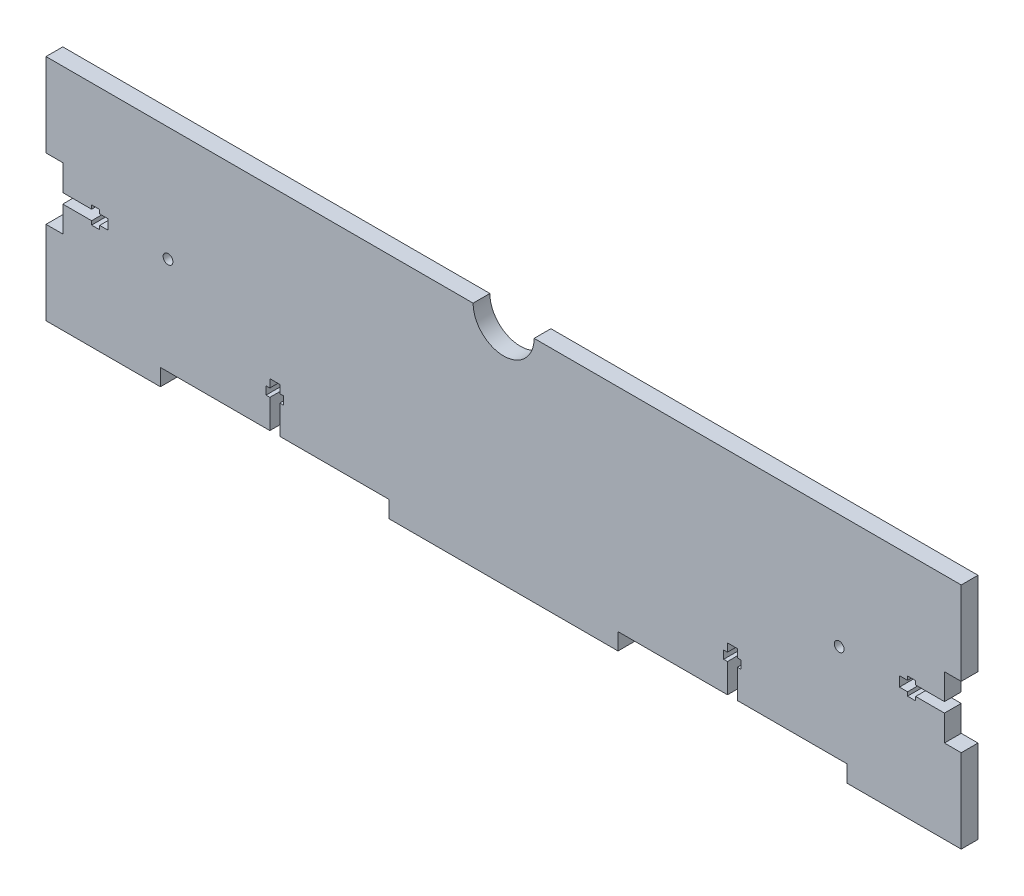
SolidWorks part; units mm, degrees
ref_plane "Front Plane" through (0, 0, 0) normal (0, 0, 1) x (1, 0, 0)
ref_plane "Top Plane" through (0, 0, 0) normal (0, 1, 0) x (1, 0, 0)
ref_plane "Right Plane" through (0, 0, 0) normal (1, 0, 0) x (0, 0, -1)
sketch "Sketch1" plane through (0, 0, 0) normal (0, 0, 1) x (1, 0, 0)
  line L0 (0, 78) -> (0, 50.625)
  line L1 (0, 50.625) -> (5.5, 50.625)
  line L2 (5.5, 50.625) -> (5.5, 42.125)
  line L3 (5.5, 42.125) -> (14.95, 42.125)
  line L4 (14.95, 42.125) -> (14.95, 43.375)
  line L5 (14.95, 43.375) -> (17.6, 43.375)
  line L6 (17.6, 43.375) -> (17.6, 42.125)
  line L7 (17.6, 42.125) -> (20.25, 42.125)
  line L8 (20.25, 42.125) -> (20.25, 38.875)
  line L9 (20.25, 38.875) -> (17.6, 38.875)
  line L10 (17.6, 38.875) -> (17.6, 37.625)
  line L11 (17.6, 37.625) -> (14.95, 37.625)
  line L12 (14.95, 37.625) -> (14.95, 38.875)
  line L13 (14.95, 38.875) -> (5.5, 38.875)
  line L14 (5.5, 38.875) -> (5.5, 30.375)
  line L15 (5.5, 30.375) -> (0, 30.375)
  line L16 (0, 30.375) -> (0, 3)
  line L17 (0, 3) -> (37.5, 3)
  line L18 (37.5, 3) -> (37.5, 8.5)
  line L19 (37.5, 8.5) -> (73.375, 8.5)
  line L20 (73.375, 8.5) -> (73.375, 17.95)
  line L21 (73.375, 17.95) -> (72.125, 17.95)
  line L22 (72.125, 17.95) -> (72.125, 20.6)
  line L23 (72.125, 20.6) -> (73.375, 20.6)
  line L24 (73.375, 20.6) -> (73.375, 23.25)
  line L25 (73.375, 23.25) -> (76.625, 23.25)
  line L26 (76.625, 23.25) -> (76.625, 20.6)
  line L27 (76.625, 20.6) -> (77.875, 20.6)
  line L28 (77.875, 20.6) -> (77.875, 17.95)
  line L29 (77.875, 17.95) -> (76.625, 17.95)
  line L30 (76.625, 17.95) -> (76.625, 8.5)
  line L31 (76.625, 8.5) -> (112.5, 8.5)
  line L32 (112.5, 8.5) -> (112.5, 3)
  line L33 (112.5, 3) -> (187.5, 3)
  line L34 (187.5, 3) -> (187.5, 8.5)
  line L35 (187.5, 8.5) -> (223.375, 8.5)
  line L36 (223.375, 8.5) -> (223.375, 17.95)
  line L37 (223.375, 17.95) -> (222.125, 17.95)
  line L38 (222.125, 17.95) -> (222.125, 20.6)
  line L39 (222.125, 20.6) -> (223.375, 20.6)
  line L40 (223.375, 20.6) -> (223.375, 23.25)
  line L41 (223.375, 23.25) -> (226.625, 23.25)
  line L42 (226.625, 23.25) -> (226.625, 20.6)
  line L43 (226.625, 20.6) -> (227.875, 20.6)
  line L44 (227.875, 20.6) -> (227.875, 17.95)
  line L45 (227.875, 17.95) -> (226.625, 17.95)
  line L46 (226.625, 17.95) -> (226.625, 8.5)
  line L47 (226.625, 8.5) -> (262.5, 8.5)
  line L48 (262.5, 8.5) -> (262.5, 3)
  line L49 (262.5, 3) -> (300, 3)
  line L50 (300, 3) -> (300, 30.375)
  line L51 (300, 30.375) -> (294.5, 30.375)
  line L52 (294.5, 30.375) -> (294.5, 38.875)
  line L53 (294.5, 38.875) -> (285.05, 38.875)
  line L54 (285.05, 38.875) -> (285.05, 37.625)
  line L55 (285.05, 37.625) -> (282.4, 37.625)
  line L56 (282.4, 37.625) -> (282.4, 38.875)
  line L57 (282.4, 38.875) -> (279.75, 38.875)
  line L58 (279.75, 38.875) -> (279.75, 42.125)
  line L59 (279.75, 42.125) -> (282.4, 42.125)
  line L60 (282.4, 42.125) -> (282.4, 43.375)
  line L61 (282.4, 43.375) -> (285.05, 43.375)
  line L62 (285.05, 43.375) -> (285.05, 42.125)
  line L63 (285.05, 42.125) -> (294.5, 42.125)
  line L64 (294.5, 42.125) -> (294.5, 50.625)
  line L65 (294.5, 50.625) -> (300, 50.625)
  line L66 (300, 50.625) -> (300, 78)
  line L67 (300, 78) -> (0, 78)
sketch "Sketch2" plane through (0, 0, 0) normal (0, 0, 1) x (1, 0, 0)
  line L0 (300, 78) -> (0, 78) construction
  circle A0 centre (150, 78) radius 10
  dimension "D1" = 20
extrude "Boss-Extrude1" add sketch "Sketch1" along normal blind 5.5
extrude "Cut-Extrude2" cut sketch "Sketch2" along normal through all
sketch "Sketch3" plane through (0, 0, 5.5) normal (0, 0, 1) x (1, 0, 0)
  line L0 (20.25, 42.125) -> (20.25, 38.875) construction
  line L1 (0, 78) -> (0, 50.625) construction
  line L2 (300, 50.625) -> (300, 78) construction
  circle A0 centre (40, 40.5) radius 1.6
  circle A1 centre (260, 40.5) radius 1.6
  point P4 (0, 0)
  point P7 (20.25, 40.5)
  dimension "D1" = 3.2
  dimension "D2" = 40
  dimension "D3" = 40
extrude "Cut-Extrude3" cut sketch "Sketch3" against normal through all
